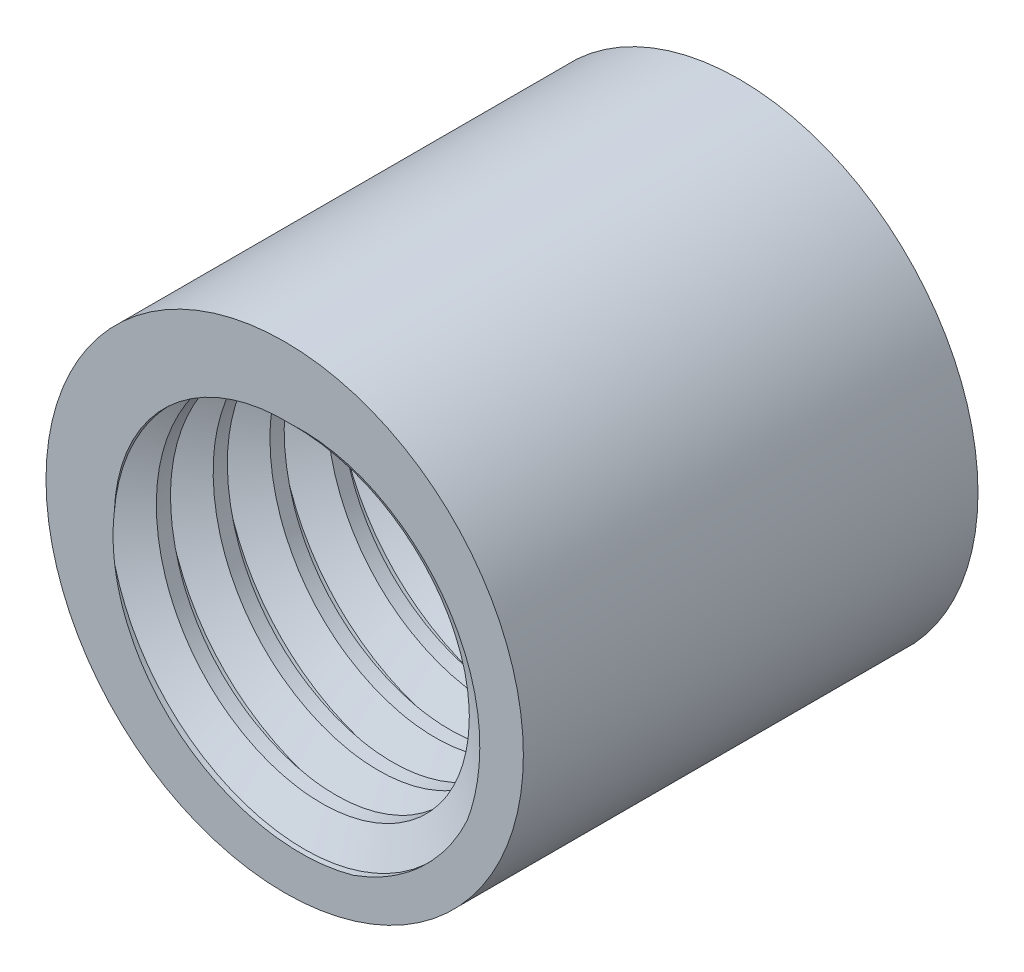
SolidWorks part; units mm, degrees
material "Brass"
ref_plane "Front Plane" through (0, 0, 0) normal (0, 0, 1) x (1, 0, 0)
ref_plane "Top Plane" through (0, 0, 0) normal (0, 1, 0) x (1, 0, 0)
ref_plane "Right Plane" through (0, 0, 0) normal (1, 0, 0) x (0, 0, -1)
sketch "Sketch1" plane through (0, 0, 0) normal (0, 0, 1) x (1, 0, 0)
  circle A0 centre (0, 0) radius 1.5
  circle A1 centre (0, 0) radius 2.1
  dimension "D1" = 3
  dimension "D2" = 4.2
extrude "Boss-Extrude1" add sketch "Sketch1" along normal blind 4
thread "Thread1" pitch 0.5 method cut profile "Thread Profile1" start angle 2, offset 1, length 10, pitch 0.5, diameter 3
ref_plane "Plane1" through (-1.4991, 0.0523, 5) normal (-0.0349, -0.9994, 0) x (-0.9994, 0.0349, 0)
sketch "Thread Profile1" plane through (-1.4991, 0.0523, 5) normal (-0.0349, -0.9994, 0) x (-0.9994, 0.0349, 0)
  line L0 (0, 0) -> (0, 0.5) construction
  line L1 (0, 0) -> (0.2706, 0.1562)
  line L2 (0.2706, 0.1562) -> (0.2706, 0.2187)
  line L3 (0.2706, 0.2187) -> (0, 0.375)
  line L4 (0.2706, 0.1875) -> (0, 0.1875) construction
  line L11 (0, 0) -> (0, 0.375)
  point P2 (0, 0)
  dimension "Pitch" = 0.5
  dimension "Profile_Angle" = 60
  dimension "Profile_Land" = 0.0625
  dimension "Profile_Height" = 0.2706
sketch "Sketch2" plane through (0, 0, 4) normal (0, 0, 1) x (1, 0, 0)
  circle A0 centre (0, 0) radius 2.1 construction
  arc A1 (-0.2088, 2.0896) -> (0.5516, 2.0263) centre (0.2903, 3.4864) ccw
  arc A2 (1.0047, 1.6159) -> (1.6486, 1.2064) centre (2.0958, 2.6208) ccw
  arc A3 (1.8591, 0.6325) -> (2.2389, -0.0293) centre (3.2922, 1.0152) ccw
  arc A4 (2.1586, -0.6354) -> (2.1874, -1.3979) centre (3.6054, -0.9625) ccw
  arc A5 (1.8346, -1.8971) -> (1.5057, -2.5857) centre (2.9637, -2.8592) ccw
  arc A6 (0.9613, -2.8638) -> (0.3502, -3.3207) centre (1.514, -4.2404) ccw
  arc A7 (-0.2611, -3.314) -> (-1.0146, -3.4345) centre (-0.4115, -4.7897) ccw
  arc A8 (-1.5528, -3.1444) -> (-2.2759, -2.901) centre (-2.3717, -4.3812) ccw
  arc A9 (-2.6177, -2.3941) -> (-3.1449, -1.8424) centre (-3.9176, -3.1086) ccw
  arc A10 (-3.2119, -1.2348) -> (-3.4223, -0.5013) centre (-4.695, -1.2634) ccw
  arc A11 (-3.1993, 0.0679) -> (-3.0448, 0.8151) centre (-4.5258, 0.7318) ccw
  arc A12 (-2.5827, 1.2155) -> (-2.0987, 1.8053) centre (-3.4488, 2.4198) ccw
  arc A13 (-1.5035, 1.9451) -> (-0.8008, 2.2424) centre (-1.7107, 3.4139) ccw
  circle A14 centre (0, 0) radius 5.1115
  point P40 (-0.563, -0.609)
  circle M14 centre (0, 0) radius 2.1
  dimension "D1" = 13
extrude "Cut-Extrude1" [suppressed] cut sketch "Sketch2" against normal through all contours A1 M14 | A13 M14 | A12 M14 | A11 M14 | A10 M14 | A9 M14 | A8 M14 | A7 M14 | A6 M14 | A5 M14 | A4 M14 | A3 M14 | A2 M14
